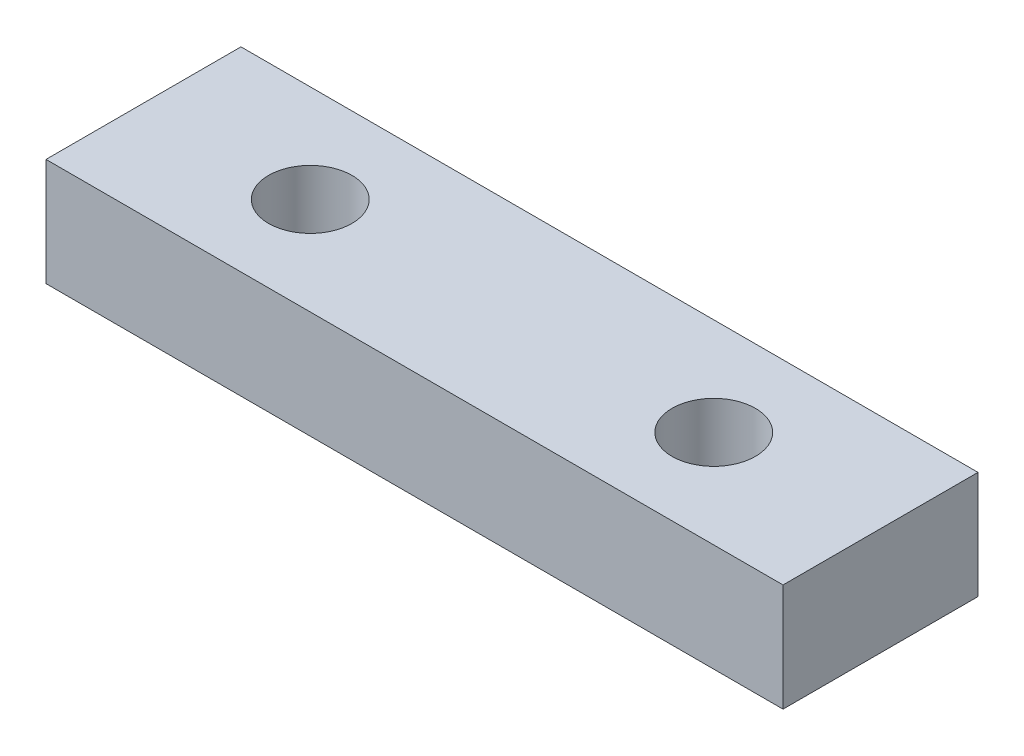
SolidWorks part; units mm, degrees
material "PLA Black"
ref_plane "Front" through (0, 0, 0) normal (0, 0, 1) x (1, 0, 0)
ref_plane "Top" through (0, 0, 0) normal (0, 1, 0) x (1, 0, 0)
ref_plane "Right" through (0, 0, 0) normal (1, 0, 0) x (0, 0, -1)
sketch "Sketch1" plane through (0, 0, 0) normal (0, 1, 0) x (1, 0, 0)
  line L0 (-13.9058, -3.6239) -> (9.3641, -3.6239) construction
  line L1 (0, 6.301) -> (0, -4.9245) construction
  line L2 (13.7, 0) -> (13.7, -7.2479) construction
  line L3 (-13.7, 0) -> (13.7, 0)
  line L4 (-13.7, 0) -> (-13.7, -7.2479)
  line L5 (-13.7, -7.2479) -> (13.7, -7.2479)
  line L6 (13.7, 0) -> (13.7, -7.2479)
  line L7 (-13.7, -7.2479) -> (13.7, -7.2479) construction
  circle A0 centre (7.5, -3.6239) radius 1.55
  circle A1 centre (-7.5, -3.6239) radius 1.55
  dimension "D3" = 3.1
  dimension "D4" = 15
extrude "Boss-Extrude1" add sketch "Sketch1" along normal blind 4 contours L3 L6 L5 L4 | A1 | A0
